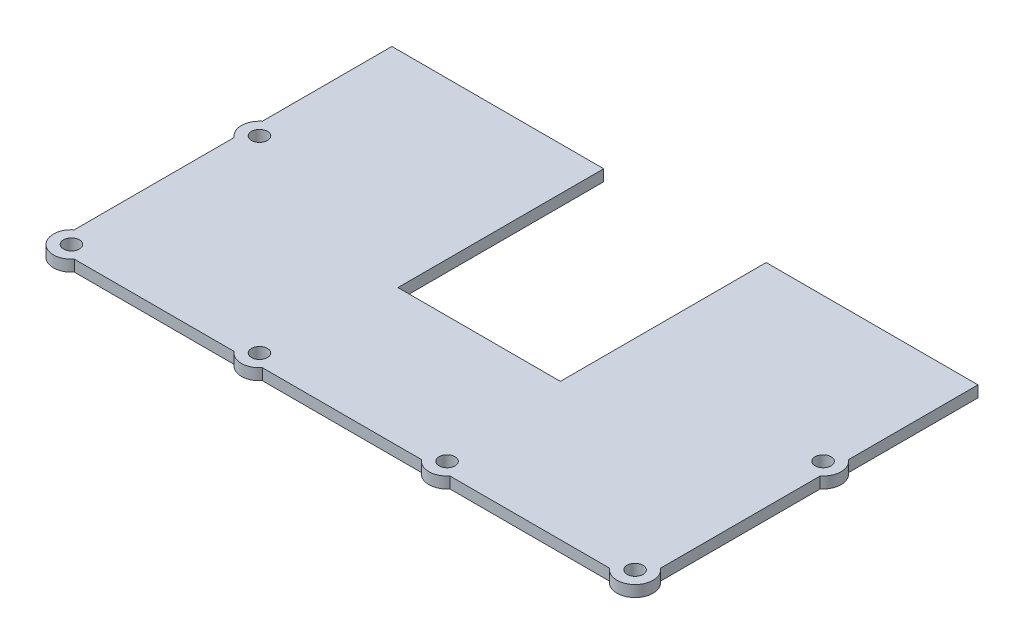
SolidWorks part; units mm, degrees
material "UHMW"
ref_plane "Front Plane" through (0, 0, 0) normal (0, 0, 1) x (1, 0, 0)
ref_plane "Top Plane" through (0, 0, 0) normal (0, 1, 0) x (1, 0, 0)
ref_plane "Right Plane" through (0, 0, 0) normal (1, 0, 0) x (0, 0, -1)
sketch "Sketch1" plane through (0, 0, 0) normal (0, 1, 0) x (1, 0, 0)
  circle A0 centre (3.175, -40.4401) radius 2.2479
  circle A1 centre (3.175, -93.3568) radius 2.2479
  circle A2 centre (56.0917, -93.3568) radius 2.2479
  circle A3 centre (108.8828, -93.3568) radius 2.2479
  circle A4 centre (161.7995, -93.3568) radius 2.2479
  circle A5 centre (161.7995, -40.4401) radius 2.2479
  line B0 (59.6265, 0) -> (0, 0)
  line B1 (59.6265, 0) -> (59.6265, -57.9238)
  line B2 (164.9745, -36.4745) -> (164.9745, 0)
  line B3 (164.9745, -89.3912) -> (164.9745, -44.4057)
  line B4 (112.8484, -96.5318) -> (157.8339, -96.5318)
  line B5 (101.6, -96.5318) -> (104.9173, -96.5318)
  line B6 (101.6, -96.5318) -> (95.25, -96.5318)
  line B7 (69.85, -96.5318) -> (95.25, -96.5318)
  line B8 (69.85, -96.5318) -> (63.5, -96.5318)
  line B9 (60.0572, -96.5318) -> (63.5, -96.5318)
  line B10 (7.1406, -96.5318) -> (52.1261, -96.5318)
  line B11 (0, -44.4057) -> (0, -89.3912)
  line B12 (0, 0) -> (0, -36.4745)
  line B13 (164.9745, 0) -> (105.348, 0)
  line B14 (105.348, 0) -> (105.348, -57.9238)
  line B15 (59.6265, -57.9238) -> (105.348, -57.9238)
  arc B16 (164.9745, -44.4057) -> (164.9745, -36.4745) centre (161.7995, -40.4401) ccw
  arc B17 (157.8339, -96.5318) -> (164.9745, -89.3912) centre (161.7995, -93.3568) ccw
  arc B18 (104.9173, -96.5318) -> (112.8484, -96.5318) centre (108.8828, -93.3568) ccw
  arc B19 (52.1261, -96.5318) -> (60.0572, -96.5318) centre (56.0917, -93.3568) ccw
  arc B20 (0, -89.3912) -> (7.1406, -96.5318) centre (3.175, -93.3568) ccw
  arc B21 (0, -36.4745) -> (0, -44.4057) centre (3.175, -40.4401) ccw
  dimension "D1" = 4.4958
sketch_block_instance "Block-topplate-1"
sketch_block "Block-topplate" parameters "D1"=72.8218, "D2"=72.8218, "D3"=25.4
extrude "Boss-Extrude1" add sketch "Sketch1" along normal blind 3.175
equation "\"Unit Measure\"= \"BoundingVolume\" / \"Thickness\"'in^2"
